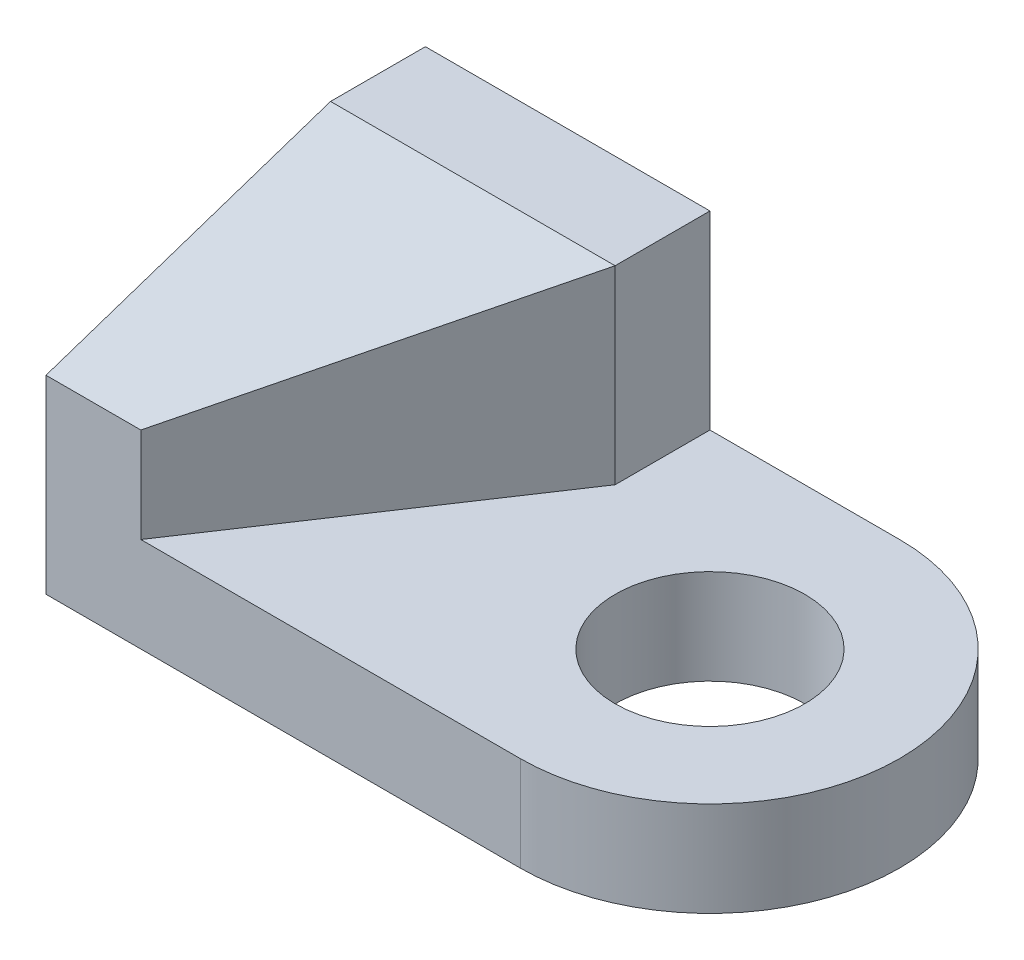
SolidWorks part; units mm, degrees
ref_plane "前基準面" through (0, 0, 0) normal (0, 0, 1) x (1, 0, 0)
ref_plane "上基準面" through (0, 0, 0) normal (0, 1, 0) x (1, 0, 0)
ref_plane "右基準面" through (0, 0, 0) normal (1, 0, 0) x (0, 0, -1)
sketch "草圖1" plane through (0, 0, 0) normal (0, 1, 0) x (1, 0, 0)
  line L0 (0, 10) -> (-25, 10)
  line L1 (-25, 10) -> (-25, -10)
  line L2 (-25, -10) -> (0, -10)
  line L3 (-25, 5) -> (-10, 5)
  line L4 (-25, 10) -> (-10, 10)
  line L5 (-25, 10) -> (-25, -10)
  line L6 (-25, -10) -> (-10, -10)
  line L7 (-10, 10) -> (-10, -10)
  circle A0 centre (0, 0) radius 5
  arc A1 (0, -10) -> (0, 10) centre (0, 0) ccw
  dimension "D1" = 10
  dimension "D2" = 20
  dimension "D3" = 25
  dimension "D4" = 15
  dimension "D5" = 5
extrude "填料-伸長1" add sketch "草圖1" along normal blind 5 contours L2 A1 L0 L7 A0 region at (9.7172, 0, 0)
extrude "填料-伸長2" add sketch "草圖1<3>" along normal blind 15 contours L7 L0 L1 L3 | L7 L3 L1 L2 region at (-17.5, 0, -7.5) region at (-17.5, 0, 2.5)
sketch "草圖1<3>" plane through (0, 0, 0) normal (0, 1, 0) x (1, 0, 0) same geometry as "草圖1"
sketch "草圖2" plane through (0, 15, 0) normal (0, 1, 0) x (1, 0, 0)
  line L0 (-25, 5) -> (-10, 5) construction
  line L1 (-25, 10) -> (-25, -10) construction
  line L2 (-10, 10) -> (-10, -10) construction
  line L3 (-10, 5) -> (-20, -10)
  line L4 (-25, -10) -> (-10, -10) construction
  line L5 (-10, 10) -> (-25, 10) construction
  line L6 (-20, -10) -> (-10, -10)
  line L7 (-10, -10) -> (-10, 5)
  dimension "D1" = 5
  dimension "D2" = 5
sketch "草圖3" plane through (-10, 0, 0) normal (1, 0, 0) x (0, 0, -1)
  line L0 (5, 15) -> (-10, 10)
  line L1 (5, 15) -> (-10, 15) construction
  line L2 (10, 15) -> (-10, 15) construction
  line L3 (-10, 15) -> (-10, 5) construction
  line L4 (-10, 10) -> (-10, 15)
  line L5 (-10, 15) -> (5, 15)
  dimension "D1" = 5
extrude "除料-伸長1" cut sketch "草圖3" against normal blind 15
extrude "除料-伸長2" cut sketch "草圖2" against normal blind 10
scale "縮放比例1" scale about centroid uniform scaling yes scale factor 0.2
